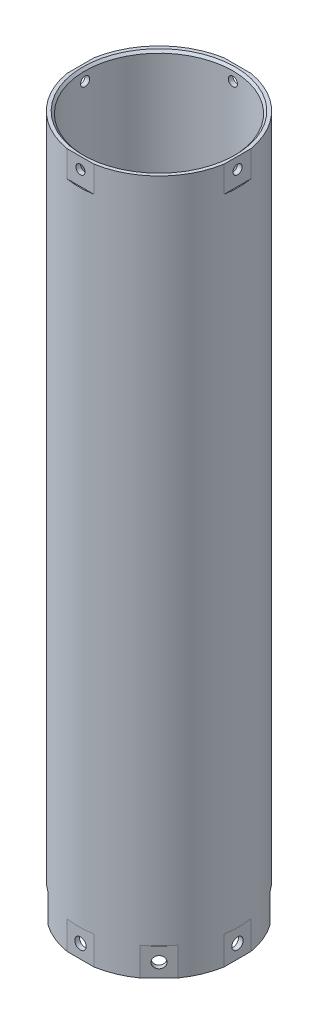
SolidWorks part; units mm, degrees
material "1060 Alloy"
ref_plane "Front Plane" through (0, 0, 0) normal (0, 0, 1) x (1, 0, 0)
ref_plane "Top Plane" through (0, 0, 0) normal (0, 1, 0) x (1, 0, 0)
ref_plane "Right Plane" through (0, 0, 0) normal (1, 0, 0) x (0, 0, -1)
sketch "Sketch2" plane through (0, 0, 0) normal (0, 0, 1) x (1, 0, 0)
  line L0 (0, 0) -> (0, 365.76) construction
  line L3 (41.275, 0) -> (44.45, 0)
  line L5 (41.275, 387.858) -> (44.45, 387.858)
  line L6 (44.45, 0) -> (44.45, 387.858)
  line L11 (41.275, 387.858) -> (41.275, 193.929)
  line L12 (41.275, 193.929) -> (41.2565, 193.9033)
  line L13 (41.275, 193.929) -> (41.275, 0)
  line L14 (0, -55) -> (0, 55) construction
  dimension "D3" = 3.175
  dimension "D4" = 387.858
revolve "Revolve1" add sketch "Sketch2" angle 360 about L0 region at (42.8625, 193.929, 0)
ref_axis "Axis1" through (0, -17.0472, 0) along (0, 1, 0)
ref_plane "Plane1" through (0, 7.62, 0) normal (0, -1, 0) x (-1, 0, 0)
ref_axis "Axis2" through (0, 7.62, 88.99) along (0, 0, -1)
hole_wizard "1/4 (0.25) Diameter Hole1" positions "3DSketch1" profile "Sketch3" hole size "1/4" standard "ANSI Inch" end condition up to next
sketch3d "3DSketch1"
  line L0 (0, 7.62, 88.99) -> (0, 7.62, -88.99) construction
  point P0 (0, 7.62, -44.45)
sketch "Sketch3" plane through (0, 7.62, -44.45) normal (1, 0, 0) x (0, 1, 0)
  line L0 (0, 0) -> (0, 3.175)
  line L1 (0, 3.175) -> (3.175, 3.175)
  line L2 (3.175, 3.175) -> (3.175, 0)
  line L5 (3.175, 0) -> (0, 0)
  line L11 (0, -6.35) -> (0, 107.95) construction
  dimension "Thru Hole Dia." = 6.35
  dimension "Thru Hole Depth" = 3.175
ref_plane "Plane2" through (0, 381.508, 0) normal (0, 1, 0) x (1, 0, 0)
ref_axis "Axis3" through (0, 381.508, -48.895) along (0, 0, 1)
sketch "Sketch4" plane through (0, 0, 0) normal (0, 0, 1) x (1, 0, 0)
  line L0 (0, -17.0472) -> (0, 357.9914) construction
  line L1 (0, 381.508) -> (-43.7642, 381.508)
  line L2 (0, 381.508) -> (0, 378.46)
  line L3 (0, 378.46) -> (-43.7642, 378.46)
  line L4 (-43.7642, 381.508) -> (-43.7642, 378.46)
  line L5 (48.895, 381.508) -> (-48.895, 381.508) construction
  dimension "D1" = 43.7642
  dimension "D2" = 3.048
revolve "Cut-Revolve2" [suppressed] cut sketch "Sketch4" angle 360 about axis through (0, -17.0472, 0) along (0, 1, 0)
hole_wizard "Tap Drill for 1/4-20 Tap1" positions "3DSketch3" profile "Sketch6" hole size "1/4-20" standard "ANSI Inch"
sketch3d "3DSketch3"
  line L0 (0, 381.508, -48.895) -> (0, 381.508, 48.895) construction
  point P0 (0, 381.508, -44.45)
sketch "Sketch6" plane through (0, 381.508, -44.45) normal (1, 0, 0) x (0, 1, 0)
  line L0 (0, 0) -> (0, 4.8358)
  line L1 (0, 4.8358) -> (2.5527, 3.302)
  line L2 (2.5527, 3.302) -> (2.5527, 0)
  line L5 (2.5527, 0) -> (0, 0)
  line L10 (0, 4.8358) -> (-2.5527, 3.302) construction
  line L11 (0, -6.35) -> (0, 107.95) construction
  dimension "Hole Dia." = 5.1054
  dimension "Hole Depth" = 3.302
  dimension "Drill Angle" = 118
pattern_circular "CirPattern2" count 4 over 360 about axis through (0, -17.0472, 0) along (0, 1, 0) of "Tap Drill for 1/4-20 Tap1" reverse direction yes
chamfer "Chamfer1" distance 1.27 angle 45 2 edges at (0, 0, -41.275) (0, 387.858, -41.275)
ref_plane "Plane3" through (44.45, 0, 0) normal (1, 0, 0) x (0, 0, -1)
pattern_circular "CirPattern1" count 8 over 360 about axis through (0, -17.0472, 0) along (0, 1, 0) of "1/4 (0.25) Diameter Hole1"
sketch "Sketch7" plane through (44.45, 0, 0) normal (1, 0, 0) x (0, 0, -1)
  line L1 (8.255, -0.635) -> (-8.255, -0.635)
  line L2 (8.255, -0.635) -> (8.255, 15.875)
  line L3 (8.255, 15.875) -> (-8.255, 15.875)
  line L4 (-8.255, -0.635) -> (-8.255, 15.875)
  circle A0 centre (0, 7.62) radius 3.175 construction
  point P8 (2.3767, 7.7713)
  dimension "D1" = 8.255
  dimension "D2" = 8.255
  dimension "D4" = 8.255
  dimension "D3" = 8.255
extrude "Cut-Extrude1" cut sketch "Sketch7" against normal blind 0.635
sketch "Sketch8" plane through (44.45, 0, 0) normal (1, 0, 0) x (0, 0, -1)
  line L1 (8.255, 373.253) -> (-8.255, 373.253)
  line L2 (8.255, 373.253) -> (8.255, 389.763)
  line L3 (8.255, 389.763) -> (-8.255, 389.763)
  line L4 (-8.255, 373.253) -> (-8.255, 389.763)
  circle A0 centre (0, 381.508) radius 2.5527 construction
  dimension "D1" = 8.255
  dimension "D2" = 8.255
  dimension "D3" = 8.255
  dimension "D4" = 8.255
extrude "Cut-Extrude2" cut sketch "Sketch8" against normal blind 0.635
pattern_circular "CirPattern4" count 8 over 360 about axis through (0, -17.0472, 0) along (0, 1, 0) of "Cut-Extrude1"
pattern_circular "CirPattern5" count 4 over 360 about axis through (0, -17.0472, 0) along (0, 1, 0) of "Cut-Extrude2"
